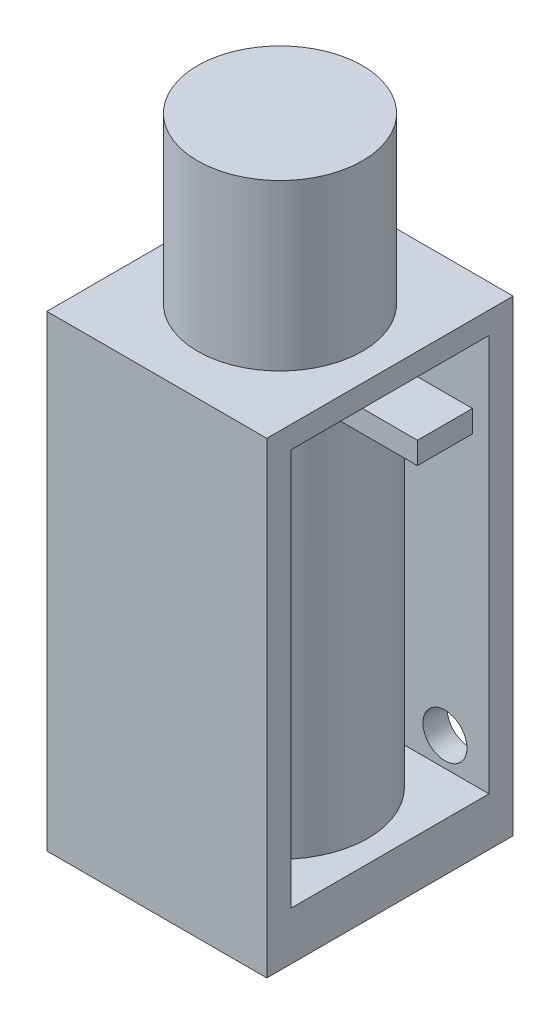
SolidWorks part; units mm, degrees
ref_plane "Front" through (0, 0, 0) normal (0, 0, 1) x (1, 0, 0)
ref_plane "Top" through (0, 0, 0) normal (0, 1, 0) x (1, 0, 0)
ref_plane "Right" through (0, 0, 0) normal (1, 0, 0) x (0, 0, -1)
sketch "Sketch2" plane through (0, 0, 0) normal (0, 1, 0) x (1, 0, 0)
  circle A0 centre (0, 0) radius 4
  dimension "D1" = 8
extrude "Boss-Extrude1" add sketch "Sketch2" along normal blind 18
sketch "Sketch3" plane through (0, 0, 0) normal (1, 0, 0) x (0, 0, -1)
  line L0 (0, -2.2) -> (0, 0) construction
  line L1 (-4.5, 0) -> (4.5, 0)
  line L2 (-4.5, 0) -> (-4.5, 18.05)
  line L3 (-4.5, 18.05) -> (4.5, 18.05)
  line L4 (4.5, 0) -> (4.5, 18.05)
  line L5 (-5.6, 19.05) -> (5.6, 19.05)
  line L6 (-5.6, 19.05) -> (-5.6, -2.2)
  line L7 (-5.6, -2.2) -> (5.6, -2.2)
  line L8 (5.6, 19.05) -> (5.6, -2.2)
  dimension "D1" = 9
  dimension "D2" = 11.2
  dimension "D3" = 2.2
  dimension "D4" = 1
  dimension "D5" = 21.25
extrude "Boss-Extrude2" add sketch "Sketch3" along normal mid plane 10
sketch "Sketch4" plane through (0, 0, 0) normal (0, 1, 0) x (1, 0, 0)
  circle A0 centre (0, 0) radius 3.75
  circle A1 centre (0, 0) radius 1.5
  dimension "D1" = 7.5
  dimension "D2" = 3
extrude "Boss-Extrude3" add sketch "Sketch4" along normal blind 7.5 from surface contours A0 starting at face at (0, 19.05, 0)
extrude "Boss-Extrude4" add sketch "Sketch4<3>" against normal blind 1.5 from surface contours A1 region at (0, 0, 0) starting at face at (0, -2.2, 0)
sketch "Sketch4<3>" plane through (0, 0, 0) normal (0, 1, 0) x (1, 0, 0) same geometry as "Sketch4"
sketch "Sketch5" plane through (0, 0, -5.6) normal (0, 0, -1) x (-1, 0, 0)
  line L0 (-5, -2.2) -> (5, -2.2) construction
  line L1 (-5, -2.2) -> (-5, 19.05) construction
  line L2 (5, -2.2) -> (5, 19.05) construction
  circle A0 centre (-3, 1.3) radius 1
  circle A1 centre (3, 11.3) radius 1
  dimension "D1" = 2
  dimension "D4" = 2
  dimension "D2" = 3.5
  dimension "D3" = 2
  dimension "D5" = 2
  dimension "D6" = 10
extrude "Cut-Extrude1" cut sketch "Sketch5" against normal up to surface (1.1 mm away) up to face at (0, 9.025, -4.5)
sketch "Sketch6" plane through (0, 18.05, 0) normal (0, -1, 0) x (1, 0, 0)
  line L0 (5, -4.5) -> (5, 4.5) construction
  line L1 (5, -4.5) -> (5, 4.5)
  line L2 (3, 0) -> (5, 0) construction
  line L3 (3, 1.25) -> (7.5, 1.25)
  line L4 (3, 1.25) -> (3, -1.25)
  line L5 (3, -1.25) -> (7.5, -1.25)
  line L6 (7.5, 1.25) -> (7.5, -1.25)
  line M9 (5, -4.5) -> (5, 4.5)
  dimension "D1" = 2.5
  dimension "D2" = 2.5
  dimension "D3" = 2
extrude "Boss-Extrude6" add sketch "Sketch6" along normal blind 1 contours L6 L3 L1 L5 M9 | L2 L4 L5 L1 | L4 L2 L3 M9 region at (4, 18.05, -0.625) region at (6.25, 18.05, 0) region at (4, 18.05, 0.625)
